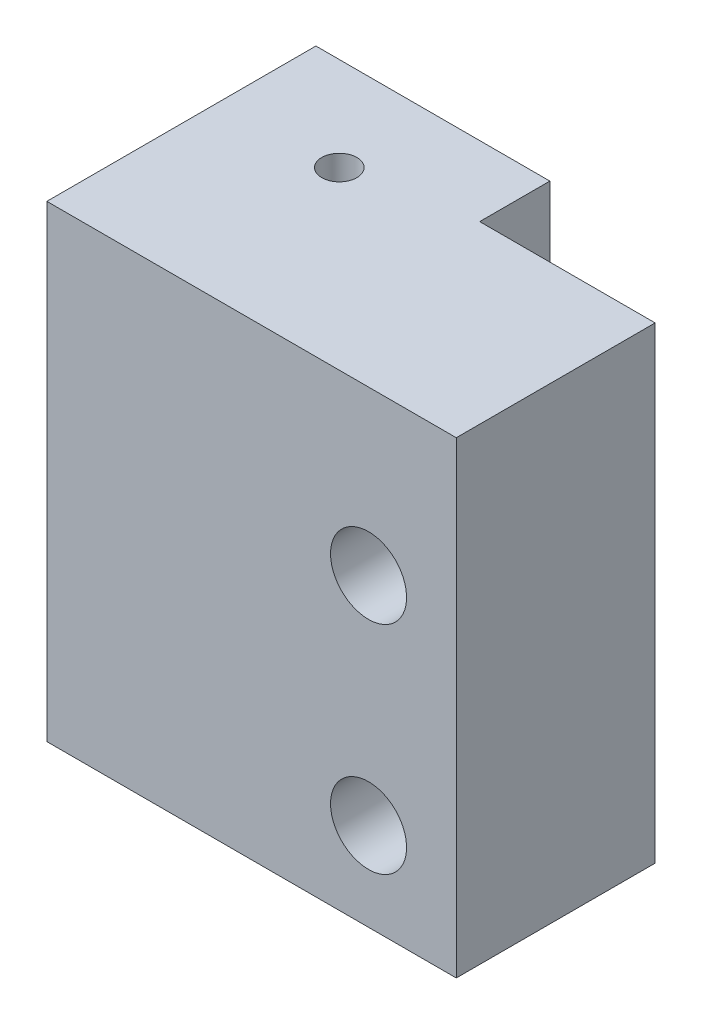
SolidWorks part; units mm, degrees
ref_plane "Front Plane" through (0, 0, 0) normal (0, 0, 1) x (1, 0, 0)
ref_plane "Top Plane" through (0, 0, 0) normal (0, 1, 0) x (1, 0, 0)
ref_plane "Right Plane" through (0, 0, 0) normal (1, 0, 0) x (0, 0, -1)
sketch "Sketch1" plane through (0, 0, 0) normal (0, 1, 0) x (1, 0, 0)
  line L5 (-10, -5.2575) -> (-10, 0.7425)
  line L6 (-10, 0.7425) -> (10, 0.7425)
  line L9 (25, -5.2575) -> (25, -22.2575)
  line L10 (0, -22.2575) -> (0, 0.7425) construction
  line L11 (-10, -5.2575) -> (-10, -22.2575)
  line L12 (10, 0.7425) -> (10, -5.2575)
  line L13 (10, -5.2575) -> (25, -5.2575)
  line L14 (-10, -22.2575) -> (25, -22.2575)
  point P2 (0, 0)
  dimension "D5" = 17
  dimension "D6" = 15
extrude "Boss-Extrude2" add sketch "Sketch1" along normal blind 40
sketch "Sketch3" plane through (0, 0, 0) normal (0, -1, 0) x (1, 0, 0)
  line L0 (0, -0.7425) -> (0, 22.2575) construction
  line L1 (10, -0.7425) -> (-10, -0.7425) construction
  circle A0 centre (0, 7.2575) radius 4
  dimension "D1" = 8
  dimension "D2" = 8
extrude "Cut-Extrude1" cut sketch "Sketch3" against normal blind 35
sketch "Sketch4" plane through (0, 0, 5.2575) normal (0, 0, -1) x (-1, 0, 0)
  line L0 (-25, 20) -> (-10, 20) construction
  line L1 (-25, 40) -> (-25, 0) construction
  line L2 (-10, 40) -> (-10, 0) construction
  line L3 (-17.5, 40) -> (-17.5, 0) construction
  line L4 (-25, 40) -> (-10, 40) construction
  line L5 (-25, 0) -> (-10, 0) construction
  circle A0 centre (-17.5, 26.0458) radius 3.25
  circle A2 centre (-17.5, 7.5353) radius 3.25
  dimension "D1" = 6.5
  dimension "D2" = 6.5
extrude "Cut-Extrude2" cut sketch "Sketch4" against normal up to next
sketch "Sketch5" plane through (0, 0, 0) normal (0, -1, 0) x (1, 0, 0)
  line L0 (0, -0.7425) -> (0, 22.2575) construction
  line L1 (10, -0.7425) -> (-10, -0.7425) construction
  line L2 (-10, 22.2575) -> (25, 22.2575) construction
sketch "Sketch6" plane through (0, 35, 0) normal (0, -1, 0) x (1, 0, 0)
  circle A0 centre (0, 7.2575) radius 1.5
  dimension "D1" = 3
extrude "Cut-Extrude3" cut sketch "Sketch6" against normal blind 10
